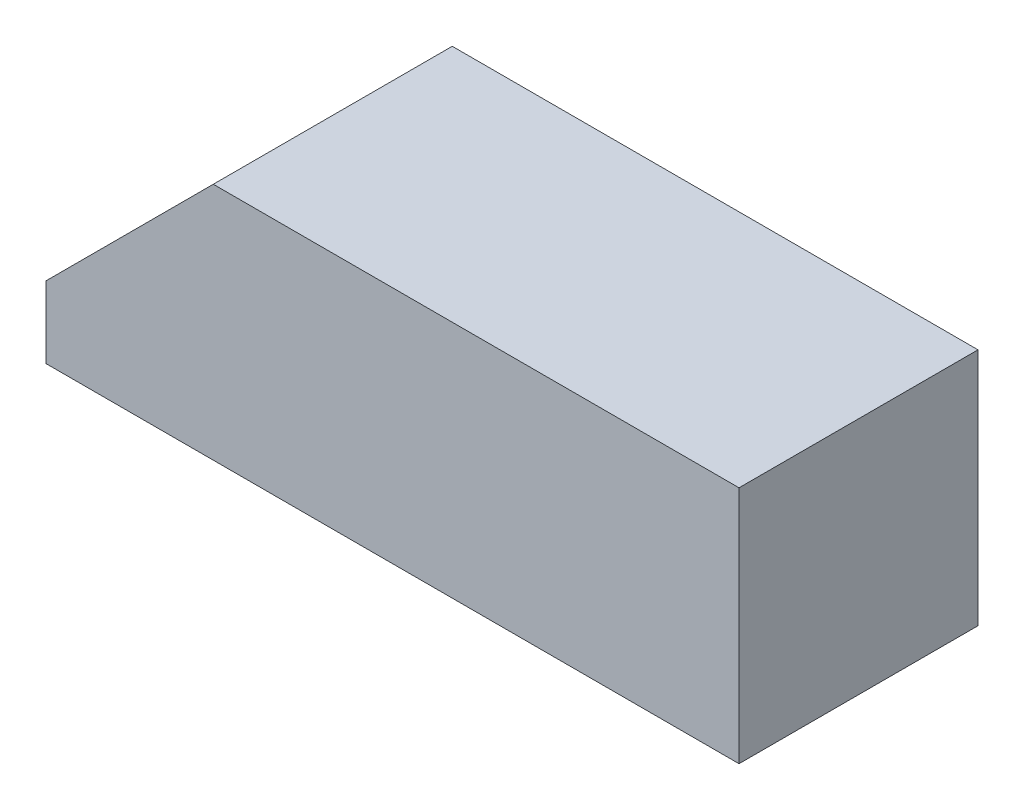
SolidWorks part; units mm, degrees
material "K110"
ref_plane "Front Plane" through (0, 0, 0) normal (0, 0, 1) x (1, 0, 0)
ref_plane "Top Plane" through (0, 0, 0) normal (0, 1, 0) x (1, 0, 0)
ref_plane "Right Plane" through (0, 0, 0) normal (1, 0, 0) x (0, 0, -1)
sketch "Sketch1" plane through (0, 0, 0) normal (0, 0, 1) x (1, 0, 0)
  line L1 (-72.5, -25) -> (72.5, -25)
  line L2 (-72.5, -25) -> (-72.5, 25)
  line L3 (-72.5, 25) -> (72.5, 25)
  line L4 (72.5, -25) -> (72.5, 25)
  line L5 (-72.5, -25) -> (72.5, 25) construction
  line L6 (-72.5, 25) -> (72.5, -25) construction
  point P0 (0, 0)
  dimension "D1" = 50
  dimension "D2" = 145
extrude "Boss-Extrude1" add sketch "Sketch1" along normal mid plane 50
sketch "Sketch2" plane through (0, 0, 0) normal (0, 0, 1) x (1, 0, 0)
  line L0 (-72.5, -10) -> (-37.5, 25)
  line L1 (-72.5, 25) -> (-72.5, -25) construction
  line L2 (72.5, 25) -> (-72.5, 25) construction
  line L3 (-37.5, 25) -> (-72.5, 25)
  line L4 (-72.5, 25) -> (-72.5, -10)
  dimension "D1" = 45
  dimension "D2" = 35
extrude "Cut-Extrude1" cut sketch "Sketch2" against normal through all both and the other way through all
hole_wizard "Ø12.0 (12) Diameter Hole1" positions "Sketch9" profile "Sketch4" hole size "Ø12.0" standard "ISO"
sketch "Sketch9" plane through (-72.5, 0, 0) normal (-1, 0, 0) x (0, 0, 1)
  line L0 (25, -25) -> (-25, -25) construction
  point P0 (0, -5)
  dimension "D1" = 20
sketch "Sketch4" plane through (-72.5, -5, 0) normal (0, 1, 0) x (0, 0, 1)
  line L0 (0, 0) -> (0, 18)
  line L1 (0, 18) -> (6, 18)
  line L2 (6, 18) -> (6, 0)
  line L5 (6, 0) -> (0, 0)
  line L10 (0, 18) -> (-6, 18) construction
  line L11 (0, -6.35) -> (0, 107.95) construction
  dimension "Hole Dia." = 12
  dimension "Hole Depth" = 18
  dimension "Drill Angle" = 180
hole_wizard "M10 Tapped Hole2" positions "Sketch12" profile "Sketch11" tap size "M10" standard "ISO"
sketch "Sketch12" plane through (-54.5, 0, 0) normal (-1, 0, 0) x (0, 0, 1)
  point P0 (0, -5)
sketch "Sketch11" plane through (-54.5, -5, 0) normal (0, 1, 0) x (0, 0, 1)
  line L0 (0, 0) -> (0, 27.5)
  line L1 (0, 27.5) -> (4.25, 24.9463)
  line L2 (4.25, 24.9463) -> (4.25, 0)
  line L5 (4.25, 0) -> (0, 0)
  line L10 (0, 27.5) -> (-4.25, 24.9463) construction
  line L11 (0, -6.35) -> (0, 107.95) construction
  dimension "Tap Drill Dia." = 8.5
  dimension "Tap Drill Depth" = 27.5
  dimension "Drill Angle" = 118
cosmetic thread "Hole Thread3"
